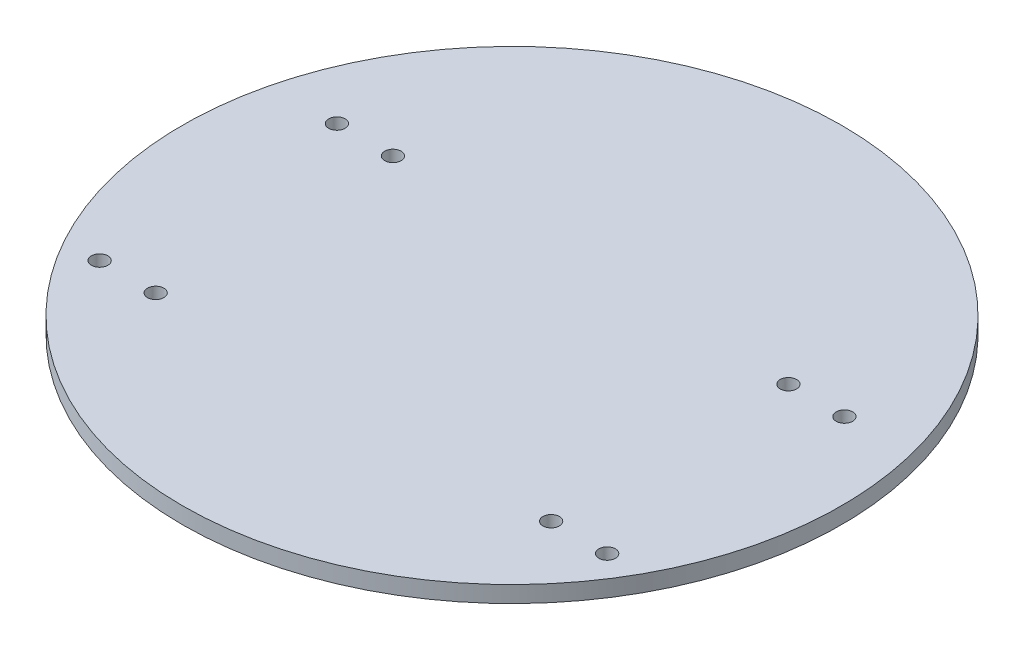
SolidWorks part; units mm, degrees
ref_plane "Front Plane" through (0, 0, 0) normal (0, 0, 1) x (1, 0, 0)
ref_plane "Top Plane" through (0, 0, 0) normal (0, 1, 0) x (1, 0, 0)
ref_plane "Right Plane" through (0, 0, 0) normal (1, 0, 0) x (0, 0, -1)
sketch "Sketch1" plane through (0, 0, 0) normal (0, 1, 0) x (1, 0, 0)
  circle A0 centre (0, 0) radius 100
  dimension "D1" = 200
extrude "Boss-Extrude1" add sketch "Sketch1" along normal blind 5
sketch "Sketch2" plane through (0, 5, 0) normal (0, 1, 0) x (1, 0, 0)
  line L0 (-100, 0) -> (100, 0) construction
  line L1 (-77, -48.1283) -> (-77, 23.8717) construction
  line L2 (0, -100) -> (0, 100) construction
  line L3 (-74.5, 23.8717) -> (-62.5, 23.8717) construction
  line L4 (-60, 23.8717) -> (-60, -48.1283) construction
  line L5 (-77, -48.1283) -> (-60, -48.1283) construction
  line L6 (77, -48.1283) -> (60, -48.1283) construction
  line L7 (60, 23.8717) -> (60, -48.1283) construction
  line L8 (77, 23.8717) -> (60, 23.8717) construction
  line L9 (77, -48.1283) -> (77, 23.8717) construction
  circle A0 centre (0, 0) radius 100 construction
  circle A1 centre (-77, -48.1283) radius 2.5
  circle A2 centre (-77, 23.8717) radius 2.5
  circle A3 centre (-60, -48.1283) radius 2.5
  circle A4 centre (-60, 23.8717) radius 2.5
  circle A5 centre (60, 23.8717) radius 2.5
  circle A6 centre (60, -48.1283) radius 2.5
  circle A7 centre (77, 23.8717) radius 2.5
  circle A8 centre (77, -48.1283) radius 2.5
  dimension "D1" = 12
  dimension "D3" = 5
  dimension "D4" = 60
  dimension "D2" = 72
extrude "Cut-Extrude1" cut sketch "Sketch2" against normal blind 10
